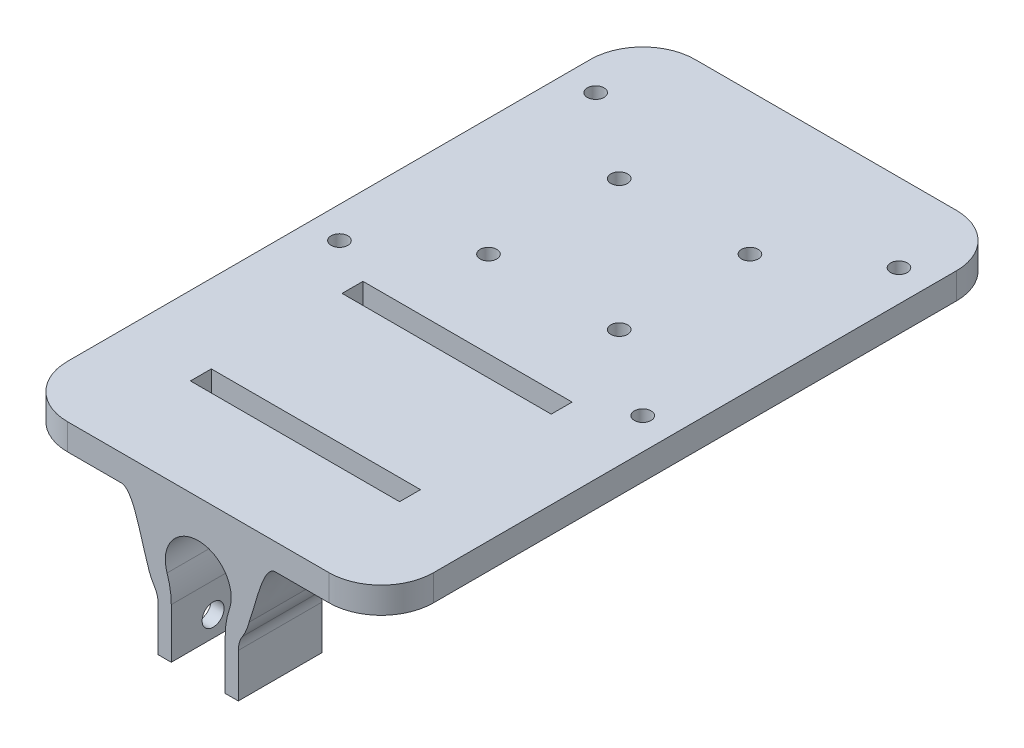
SolidWorks part; units mm, degrees
ref_plane "Front Plane" through (0, 0, 0) normal (0, 0, 1) x (1, 0, 0)
ref_plane "Top Plane" through (0, 0, 0) normal (0, 1, 0) x (1, 0, 0)
ref_plane "Right Plane" through (0, 0, 0) normal (1, 0, 0) x (0, 0, -1)
sketch "Sketch3" plane through (0, 0, 0) normal (0, 0, 1) x (1, 0, 0)
  line L0 (0, 11) -> (0, 0) construction
  line L1 (-35, 13.5) -> (35, 13.5)
  line L2 (-35, 13.5) -> (-35, 8.5)
  line L3 (-35, 8.5) -> (35, 8.5)
  line L4 (35, 13.5) -> (35, 8.5)
  line L5 (-35, 13.5) -> (35, 8.5) construction
  line L6 (-35, 8.5) -> (35, 13.5) construction
  point P0 (0, 11)
  dimension "D1" = 5
  dimension "D2" = 70
  dimension "D3" = 11
extrude "Boss-Extrude2" add sketch "Sketch3" along normal blind 120 from offset 10
sketch "Sketch1" plane through (0, 0, 0) normal (0, 0, 1) x (1, 0, 0)
  line L0 (-35, 8.5) -> (35, 8.5) construction
  line L1 (0, 0) -> (0, -9) construction
  line L2 (-14.6256, 8.5) -> (14.6256, 8.5)
  line L3 (0, 0) -> (-7.6604, -6.4279) construction
  line L4 (-35, 8.5) -> (35, 8.5) construction
  line L5 (5.1604, -16.4279) -> (5.1604, -6.8736)
  line L6 (-6.1604, -16.4279) -> (-5.1604, -16.4279)
  line L7 (-6.1604, -16.4279) -> (-7.6604, -16.4279)
  line L8 (-5.1604, -16.4279) -> (-5.1604, -6.8736)
  line L9 (-7.6604, -16.4279) -> (-7.6604, -8.0444)
  line L10 (6.1604, -16.4279) -> (7.6604, -16.4279)
  line L11 (6.1604, -16.4279) -> (5.1604, -16.4279)
  line L12 (7.6604, -16.4279) -> (7.6604, -8.0444)
  arc A0 (5.9629, -2.033) -> (-5.9629, -2.033) centre (0, 0) ccw
  arc A1 (8.4403, -5.363) -> (9.7197, -2.3512) centre (0, 0) ccw
  arc A2 (-7.6604, -8.0444) -> (-8.4403, -5.363) centre (-12.6604, -8.0444) ccw
  arc A3 (-5.1604, -6.8736) -> (-5.9629, -2.033) centre (-20.1604, -6.8736) ccw
  arc A4 (5.1604, -6.8736) -> (5.9629, -2.033) centre (20.1604, -6.8736) cw
  arc A5 (7.6604, -8.0444) -> (8.4403, -5.363) centre (12.6604, -8.0444) cw
  arc A6 (-9.7197, -2.3512) -> (-8.4403, -5.363) centre (0, 0) ccw
  spline S0 degree 3 poles (-14.6256, 8.5) (-12.253, 8.1529) (-11.0867, 1.3821) (-9.7197, -2.3512) knots 0 0 0 0 1 1 1 1
  spline S1 degree 3 poles (14.6256, 8.5) (12.253, 8.1529) (11.0867, 1.3821) (9.7197, -2.3512) knots 0 0 0 0 1 1 1 1
  point P18 (-5.1604, -3.6138)
  point P21 (5.1604, -3.6138)
  point P24 (7.6604, -6.4279)
  point P27 (9.8544, -1.7005)
  point P28 (9.7197, -2.3512)
  dimension "D1" = 12.6
  dimension "D2" = 20
  dimension "D6" = 1
  dimension "D3" = 5
  dimension "D4" = 15
  dimension "D10" = 15
  dimension "D11" = 5
  dimension "D5" = 50
  dimension "D7" = 1.5
  dimension "D8" = 10
  dimension "D9" = 12.814
extrude "Boss-Extrude3" add sketch "Sketch1" along normal blind 8 and the other way blind 8 from offset 18
ref_plane "Plane4" through (0, 0, 70) normal (0, 0, 1) x (1, 0, 0)
sketch "Sketch4" plane through (-7.6604, 0, 0) normal (-1, 0, 0) x (0, 0, 1)
  line L0 (10, -8.0444) -> (26, -16.9992) construction
  line L1 (26, -8.0444) -> (26, -16.4279) construction
  circle A0 centre (18, -12.5218) radius 2.1
  dimension "D1" = 4.2
extrude "Cut-Extrude1" cut sketch "Sketch4" against normal blind 11
mirror "Mirror2" about plane through (0, 0, 70) normal (0, 0, 1) of "Boss-Extrude3", "Cut-Extrude1"
sketch "Sketch5" plane through (0, 13.5, 0) normal (0, 1, 0) x (1, 0, 0)
  line L0 (-16.4603, -70) -> (16.4603, -70) construction
  line L1 (-29, -25) -> (29, -25) construction
  line L2 (-29, -25) -> (-29, -74) construction
  line L3 (-29, -74) -> (29, -74) construction
  line L4 (29, -25) -> (29, -74) construction
  line L5 (-29, -25) -> (29, -74) construction
  line L6 (-29, -74) -> (29, -25) construction
  line L8 (35, -10) -> (-35, -130) construction
  line L9 (-35, -10) -> (-35, -130) construction
  line L10 (35, -130) -> (-35, -130) construction
  line L11 (35, -10) -> (-35, -10) construction
  line L14 (35, -130) -> (35, -10) construction
  circle A0 centre (29, -25) radius 1.6
  circle A1 centre (29, -74) radius 1.6
  circle A2 centre (-29, -74) radius 1.6
  circle A3 centre (-29, -25) radius 1.6
  point P0 (0, -70)
  point P23 (0, -49.5)
  dimension "D3" = 3.2
  dimension "D4" = 15
  dimension "D1" = 58
  dimension "D2" = 49
  dimension "D5" = 6
sketch "Sketch6" plane through (0, 13.5, 0) normal (0, 1, 0) x (1, 0, 0)
  line L0 (-16.4603, -70) -> (16.4603, -70) construction
  line L1 (-20, -82.5) -> (20, -82.5)
  line L2 (-20, -82.5) -> (-20, -107.5) construction
  line L3 (-20, -107.5) -> (20, -107.5)
  line L4 (20, -82.5) -> (20, -107.5) construction
  line L5 (-20, -82.5) -> (20, -107.5) construction
  line L6 (-20, -107.5) -> (20, -82.5) construction
  line L9 (-20, -82.5) -> (-20, -78.5)
  line L10 (-20, -78.5) -> (20, -78.5)
  line L11 (20, -78.5) -> (20, -89.585)
  line L12 (-20, -107.5) -> (-20, -111.5)
  line L13 (-20, -111.5) -> (20, -111.5)
  line L14 (20, -111.5) -> (20, -107.5)
  line L15 (20, -82.5) -> (20, -89.585)
  point P0 (0, -95)
  dimension "D1" = 25
  dimension "D2" = 40
  dimension "D3" = 25
  dimension "D5" = 4
  dimension "D6" = 4
sketch "Sketch7" plane through (0, 13.5, 0) normal (0, 1, 0) x (1, 0, 0)
  line L0 (0, -10) -> (0, -130) construction
  line L1 (-12.5, -37) -> (12.5, -37) construction
  line L2 (-12.5, -37) -> (-12.5, -62) construction
  line L3 (-12.5, -62) -> (12.5, -62) construction
  line L4 (12.5, -37) -> (12.5, -62) construction
  line L5 (-12.5, -37) -> (12.5, -62) construction
  line L6 (-12.5, -62) -> (12.5, -37) construction
  line L7 (35, -10) -> (-35, -10) construction
  line L8 (35, -130) -> (-35, -130) construction
  circle A0 centre (12.5, -37) radius 1.6
  circle A1 centre (12.5, -62) radius 1.6
  circle A2 centre (-12.5, -62) radius 1.6
  circle A3 centre (-12.5, -37) radius 1.6
  point P0 (0, -70)
  point P12 (0, -49.5)
  dimension "D4" = 3.2
  dimension "D1" = 25
  dimension "D2" = 25
fillet "Fillet1" radius 10 4 edges at (35, 11, 10) (35, 11, 130) (-35, 11, 130) (-35, 11, 10)
extrude "Cut-Extrude2" cut sketch "Sketch5" against normal blind 11
extrude "Cut-Extrude5" cut sketch "Sketch7" against normal up to next
extrude "Cut-Extrude6" cut sketch "Sketch6" against normal up to next contours L11 L10 L9 L1 | L13 L14 L3 L12 region at (0, 13.5, 80.5) region at (0, 13.5, 109.5)
